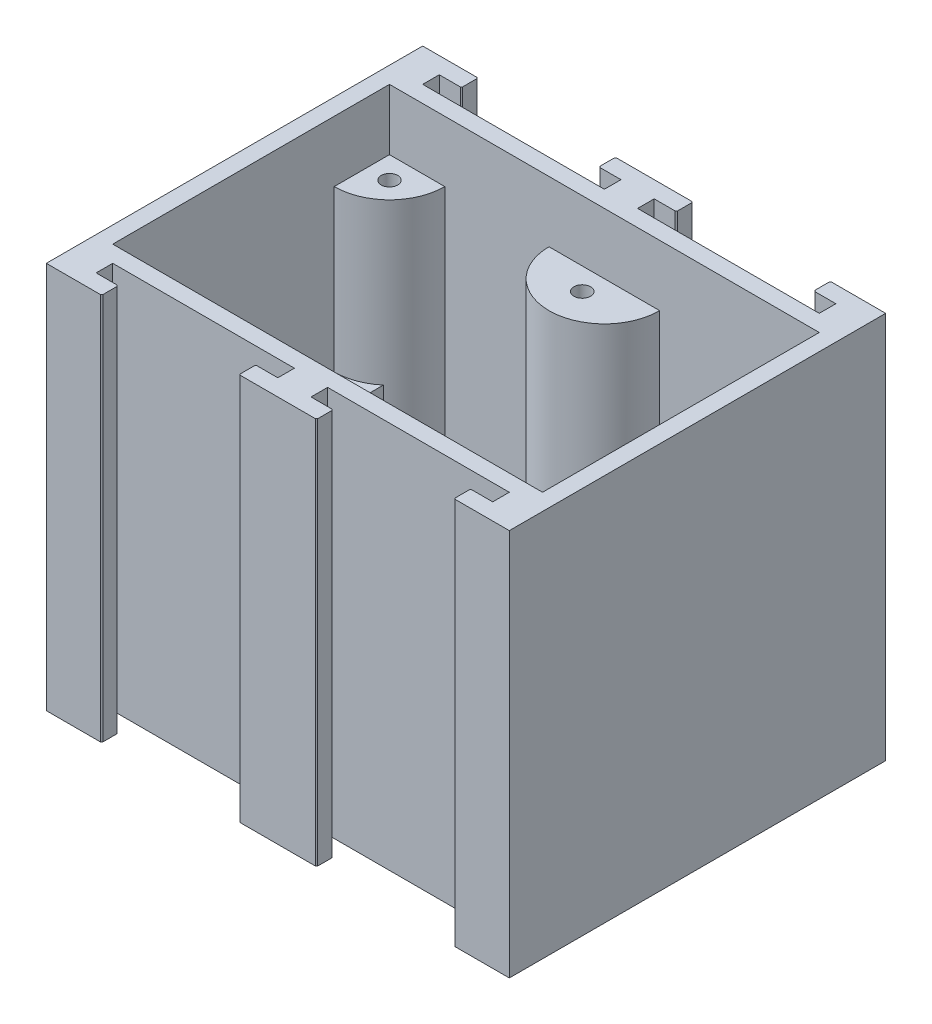
SolidWorks part; units mm, degrees
ref_plane "Front Plane" through (0, 0, 0) normal (0, 0, 1) x (1, 0, 0)
ref_plane "Top Plane" through (0, 0, 0) normal (0, 1, 0) x (1, 0, 0)
ref_plane "Right Plane" through (0, 0, 0) normal (1, 0, 0) x (0, 0, -1)
sketch "Sketch1" plane through (0, 0, 0) normal (0, 1, 0) x (1, 0, 0)
  line L0 (-38.825, 15) -> (-38.825, 25)
  line L1 (-38.825, -25) -> (-28.825, -25)
  line L2 (-38.825, -25) -> (-38.825, -15)
  line L3 (-38.825, 25) -> (-28.825, 25)
  line L4 (38.825, -25) -> (38.825, -15)
  line L5 (-38.825, -25) -> (38.825, 25) construction
  line L6 (-38.825, 25) -> (38.825, -25) construction
  line L7 (28.825, 25) -> (38.825, 25)
  line L8 (28.825, -25) -> (38.825, -25)
  line L9 (38.825, 15) -> (38.825, 25)
  line L10 (-38.825, -25) -> (-31.7539, -17.9289) construction
  line L11 (0, 0) -> (0, 50000) construction
  line L12 (0, 0) -> (-50000, 0) construction
  line L13 (10, -25) -> (-10, -25)
  line L14 (10, 25) -> (-10, 25)
  arc A0 (-28.825, -25) -> (-38.825, -15) centre (-38.825, -25) ccw
  arc A1 (-28.825, 25) -> (-38.825, 15) centre (-38.825, 25) cw
  arc A2 (38.825, -15) -> (28.825, -25) centre (38.825, -25) ccw
  arc A3 (38.825, 15) -> (28.825, 25) centre (38.825, 25) cw
  circle A4 centre (-34.825, -21) radius 1.5
  circle A5 centre (34.825, -21) radius 1.5
  circle A6 centre (34.825, 21) radius 1.5
  circle A7 centre (-34.825, 21) radius 1.5
  arc A8 (-10, -25) -> (10, -25) centre (0, -25) cw
  circle A9 centre (0, -21) radius 1.5
  circle A10 centre (0, 21) radius 1.5
  arc A11 (-10, 25) -> (10, 25) centre (0, 25) ccw
  point P0 (0, 0)
  dimension "D3" = 10
  dimension "D4" = 3
  dimension "D1" = 77.65
  dimension "D2" = 50
  dimension "D5" = 4
  dimension "D6" = 4
  dimension "D7" = 4
extrude "Boss-Extrude6" add sketch "Sketch1" along normal blind 59 contours L1 A0 L2 | A1 L3 L0 | A3 L9 L7 | L4 A2 L8 | A8 L13 A9 | L14 A11 A10 region at (-38.6836, 0, -20) region at (-38.6836, 0, 20) region at (33.825, 0, 24.8586) region at (33.825, 0, -24.8586) region at (0, 0, 24.7764) region at (0, 0, -15.2236)
sketch "Sketch2" plane through (0, 0, 0) normal (0, 1, 0) x (1, 0, 0)
  line L0 (-41.825, 28) -> (41.825, 28)
  line L1 (-38.825, -25) -> (38.825, -25)
  line L2 (-38.825, -25) -> (-38.825, 25)
  line L3 (-38.825, 25) -> (38.825, 25)
  line L4 (38.825, -25) -> (38.825, 25)
  line L5 (-38.825, -25) -> (38.825, 25) construction
  line L6 (-38.825, 25) -> (38.825, -25) construction
  line L7 (41.825, -28) -> (41.825, 28)
  line L8 (-41.825, -28) -> (41.825, -28)
  line L9 (-41.825, -28) -> (-41.825, 28)
  point P0 (0, 0)
  dimension "D2" = 83.65
  dimension "D3" = 56
  dimension "D1" = 3
extrude "Boss-Extrude7" add sketch "Sketch2" along normal blind 70
sketch "Sketch3" plane through (0, 0, 0) normal (0, 1, 0) x (1, 0, 0)
  line L0 (-38.825, 0) -> (-38.825, 19)
  line L1 (38.825, -25) -> (-38.825, -25) construction
  line L2 (38.825, -25) -> (38.825, 25) construction
  line L3 (38.825, 25) -> (-38.825, 25) construction
  line L4 (-38.825, -25) -> (-38.825, 25) construction
  line L5 (38.825, -25) -> (-38.825, 25) construction
  line L6 (38.825, 25) -> (-38.825, -25) construction
  line L7 (-38.825, 19) -> (-32.325, 19)
  line L8 (-38.825, 0) -> (-38.825, -19)
  line L9 (-38.825, -19) -> (-32.325, -19)
  line L10 (-32.325, -19) -> (-32.325, 19)
  line L11 (-11.513, 0) -> (-11.513, 50000) construction
  line L12 (-32.325, 0) -> (9.299, 0) construction
  line L13 (9.299, -25) -> (17.299, -25)
  line L14 (9.299, -25) -> (9.299, 25)
  line L15 (9.299, 25) -> (17.299, 25)
  line L16 (17.299, -25) -> (17.299, 25)
  line L17 (9.299, -25) -> (17.299, 25) construction
  line L18 (9.299, 25) -> (17.299, -25) construction
  circle A0 centre (-35.925, 4.8) radius 2.1
  circle A1 centre (-35.925, -4.8) radius 2.1
  circle A2 centre (12.899, -4.8) radius 2.1
  circle A3 centre (12.899, 4.8) radius 2.1
  point P0 (0, 0)
  point P18 (13.299, 0)
  point P25 (-11.513, 0)
  dimension "D5" = 4.2
  dimension "D1" = 6.5
  dimension "D2" = 38
  dimension "D4" = 2.9
  dimension "D6" = 9.299
  dimension "D7" = 8
extrude "Boss-Extrude8" add sketch "Sketch3" along normal blind 30
chamfer "Chamfer1" distance 3 angle 45 4 edges at (17.299, 15, 25) (13.6495, 30, 25) (17.299, 15, -25) (13.6495, 30, -25)
fillet "Fillet1" radius 3 2 edges at (9.299, 15, 21.3219) (9.299, 15, -21.3219)
sketch "Sketch4" plane through (0, 0, 0) normal (0, -1, 0) x (1, 0, 0)
  line L0 (-35.925, 4.8) -> (-35.925, -4.8) construction
  line L3 (-41.825, 28) -> (41.825, 28) construction
  line L4 (-28.825, 25) -> (-10, 25) construction
  line L5 (-35.925, 4.8) -> (12.899, 4.8) construction
  line L7 (-31.8835, 4.8) -> (-33.9043, 8.3)
  line L8 (-33.9043, 8.3) -> (-37.9457, 8.3)
  line L9 (-37.9457, 8.3) -> (-39.9665, 4.8)
  line L10 (-39.9665, 4.8) -> (-37.9457, 1.3)
  line L11 (-37.9457, 1.3) -> (-33.9043, 1.3)
  line L12 (-33.9043, 1.3) -> (-31.8835, 4.8)
  line L13 (-31.8835, -4.8) -> (-33.9043, -1.3)
  line L16 (-33.9043, -1.3) -> (-37.9457, -1.3)
  line L17 (-37.9457, -1.3) -> (-39.9665, -4.8)
  line L18 (-39.9665, -4.8) -> (-37.9457, -8.3)
  line L19 (-37.9457, -8.3) -> (-33.9043, -8.3)
  line L20 (-33.9043, -8.3) -> (-31.8835, -4.8)
  line L21 (-11.513, 4.8) -> (-11.513, 50004.8) construction
  line L22 (-37.9457, -8.3) -> (-39.9665, -4.8)
  line L23 (-31.8835, -4.8) -> (-33.9043, -8.3)
  line L24 (-33.9043, -1.3) -> (-31.8835, -4.8)
  line L25 (-39.9665, -4.8) -> (-37.9457, -1.3)
  line L26 (-37.9457, 1.3) -> (-39.9665, 4.8)
  line L27 (-31.8835, 4.8) -> (-33.9043, 1.3)
  line L28 (-33.9043, 8.3) -> (-31.8835, 4.8)
  line L29 (-39.9665, 4.8) -> (-37.9457, 8.3)
  line L30 (12.899, 4.8) -> (12.899, -4.8) construction
  line L31 (16.9405, 4.8) -> (14.9197, 8.3)
  line L32 (10.8783, 8.3) -> (8.8575, 4.8)
  line L33 (8.8575, 4.8) -> (10.8783, 1.3)
  line L34 (14.9197, 1.3) -> (16.9405, 4.8)
  line L35 (16.9405, -4.8) -> (14.9197, -1.3)
  line L36 (10.8783, -1.3) -> (8.8575, -4.8)
  line L37 (8.8575, -4.8) -> (10.8783, -8.3)
  line L38 (14.9197, -8.3) -> (16.9405, -4.8)
  line L39 (10.8783, -8.3) -> (8.8575, -4.8)
  line L40 (14.9197, -8.3) -> (10.8783, -8.3)
  line L41 (16.9405, -4.8) -> (14.9197, -8.3)
  line L42 (14.9197, -1.3) -> (16.9405, -4.8)
  line L43 (10.8783, -1.3) -> (14.9197, -1.3)
  line L44 (8.8575, -4.8) -> (10.8783, -1.3)
  line L45 (10.8783, 1.3) -> (8.8575, 4.8)
  line L46 (14.9197, 1.3) -> (10.8783, 1.3)
  line L47 (16.9405, 4.8) -> (14.9197, 1.3)
  line L48 (14.9197, 8.3) -> (16.9405, 4.8)
  line L49 (10.8783, 8.3) -> (14.9197, 8.3)
  line L50 (8.8575, 4.8) -> (10.8783, 8.3)
  circle A0 centre (-35.925, 4.8) radius 3.5 construction
  circle A1 centre (-35.925, -4.8) radius 3.5 construction
  circle A2 centre (12.899, -4.8) radius 3.5 construction
  circle A3 centre (12.899, 4.8) radius 3.5 construction
  point P24 (-11.513, 4.8)
  line M4 (9.299, 13.628) -> (9.299, -13.628)
  line M9 (-32.325, -17.4007) -> (-32.325, 17.4007)
  circle M20 centre (12.899, 4.8) radius 2.1
  circle M21 centre (12.899, -4.8) radius 2.1
  circle M22 centre (-35.925, -4.8) radius 2.1
  circle M23 centre (-35.925, 4.8) radius 2.1
  dimension "D1" = 3
  dimension "D2" = 7
  dimension "D3" = 7
extrude "Cut-Extrude2" cut sketch "Sketch4" against normal blind 16 contours L11 L12 L7 L8 L9 L10 M9 M23 | L19 L20 L13 L16 L17 L18 M9 M22 | L43 L36 L37 L40 L38 L35 M4 M21 | L49 L32 L33 L46 L34 L31 M4 M20 region at (-32.4286, 0, -4.8) region at (-32.4286, 0, 4.8) region at (15.8403, 0, 3.1018) region at (10.1784, 0, -2.7195)
fillet "Fillet2" radius 1.3 8 edges at (9.299, 8, -5.5646) (9.299, 8, 4.0354) (9.299, 8, -4.0354) (9.299, 8, 5.5646) (-32.325, 8, 5.5646) (-32.325, 8, -4.0354) (-32.325, 8, -5.5646) (-32.325, 8, 4.0354)
sketch "Sketch5" plane through (0, 0, 0) normal (0, -1, 0) x (1, 0, 0)
  line L0 (-35.925, 4.8) -> (-35.925, -4.8) construction
  line L1 (12.899, 4.8) -> (12.899, -4.8) construction
  line L2 (17.299, 22) -> (17.299, -22) construction
  line L3 (8.499, -6) -> (17.299, -6)
  line L4 (8.499, -6) -> (8.499, 6)
  line L5 (8.499, 6) -> (17.299, 6)
  line L6 (17.299, -6) -> (17.299, 6)
  line L7 (8.499, -6) -> (17.299, 6) construction
  line L8 (12.899, 0) -> (-35.925, 0) construction
  line L9 (-11.513, 0) -> (-11.513, 50000) construction
  line L10 (8.499, 6) -> (17.299, -6) construction
  line L11 (-31.525, 6) -> (-40.325, -6) construction
  line L12 (-31.525, -6) -> (-40.325, 6) construction
  line L13 (-35.925, 4.8) -> (-35.925, -4.8) construction
  line L14 (-40.325, -6) -> (-40.325, 6)
  line L15 (-31.525, 6) -> (-40.325, 6)
  line L16 (-31.525, -6) -> (-31.525, 6)
  line L17 (-31.525, -6) -> (-40.325, -6)
  point P4 (-35.925, 0)
  point P18 (-11.513, 0)
  dimension "D1" = 12
extrude "Cut-Extrude3" cut sketch "Sketch5" against normal blind 10
fillet "Fillet3" radius 0.6 8 edges at (-39.2736, 5, 6) (-40.325, 5, 6) (-39.2736, 5, -6) (-40.325, 5, -6) (16.2476, 5, -6) (17.299, 5, -6) (17.299, 5, 6) (16.2476, 5, 6)
sketch "Sketch6" plane through (0, 0, 0) normal (0, 1, 0) x (1, 0, 0)
  line L0 (0, 0) -> (0, 50000) construction
  line L1 (-41.825, -28) -> (41.825, -28) construction
  line L2 (-41.825, -28) -> (-41.825, 28) construction
  line L3 (-41.825, 28) -> (41.825, 28) construction
  line L4 (41.825, -28) -> (41.825, 28) construction
  line L5 (-41.825, -28) -> (41.825, 28) construction
  line L6 (-41.825, 28) -> (41.825, -28) construction
  line L7 (0, 0) -> (50000, 0) construction
  line L8 (38.825, 25) -> (-38.825, 25) construction
  line L9 (-3, 31) -> (3, 31)
  line L10 (-3, 31) -> (-3, 25)
  line L11 (-3, 25) -> (3, 25)
  line L12 (3, 31) -> (3, 25)
  line L13 (-3, 31) -> (3, 25) construction
  line L14 (-3, 25) -> (3, 31) construction
  line L15 (31.825, 31) -> (41.825, 34) construction
  line L16 (-7, 34) -> (7, 34)
  line L17 (-7, 34) -> (-7, 31)
  line L18 (-7, 31) -> (7, 31)
  line L19 (7, 34) -> (7, 31)
  line L20 (-7, 34) -> (7, 31) construction
  line L21 (-7, 31) -> (7, 34) construction
  line L22 (-35.825, 25) -> (-41.825, 25)
  line L23 (-35.825, 25) -> (-35.825, 31)
  line L24 (-35.825, 31) -> (-41.825, 31)
  line L25 (-41.825, 25) -> (-41.825, 31)
  line L26 (-35.825, 25) -> (-41.825, 31) construction
  line L27 (-35.825, 31) -> (-41.825, 25) construction
  line L28 (-31.825, 34) -> (-41.825, 34)
  line L29 (-31.825, 34) -> (-31.825, 31)
  line L30 (-31.825, 31) -> (-41.825, 31)
  line L31 (-41.825, 34) -> (-41.825, 31)
  line L32 (-31.825, 34) -> (-41.825, 31) construction
  line L33 (-31.825, 31) -> (-41.825, 34) construction
  line L34 (31.825, 34) -> (41.825, 31) construction
  line L35 (35.825, 31) -> (41.825, 25) construction
  line L36 (35.825, 25) -> (41.825, 31) construction
  line L37 (41.825, 34) -> (41.825, 31)
  line L38 (31.825, 31) -> (41.825, 31)
  line L39 (31.825, 34) -> (31.825, 31)
  line L40 (31.825, 34) -> (41.825, 34)
  line L41 (41.825, 25) -> (41.825, 31)
  line L42 (35.825, 31) -> (41.825, 31)
  line L43 (35.825, 25) -> (35.825, 31)
  line L44 (35.825, 25) -> (41.825, 25)
  line L45 (35.825, -25) -> (41.825, -31) construction
  line L46 (35.825, -31) -> (41.825, -25) construction
  line L47 (31.825, -34) -> (41.825, -31) construction
  line L48 (31.825, -31) -> (41.825, -34) construction
  line L49 (35.825, -25) -> (41.825, -25)
  line L50 (35.825, -25) -> (35.825, -31)
  line L51 (35.825, -31) -> (41.825, -31)
  line L52 (41.825, -25) -> (41.825, -31)
  line L53 (31.825, -34) -> (41.825, -34)
  line L54 (31.825, -34) -> (31.825, -31)
  line L55 (31.825, -31) -> (41.825, -31)
  line L56 (41.825, -34) -> (41.825, -31)
  line L57 (-31.825, -31) -> (-41.825, -34) construction
  line L58 (-31.825, -34) -> (-41.825, -31) construction
  line L59 (-35.825, -31) -> (-41.825, -25) construction
  line L60 (-35.825, -25) -> (-41.825, -31) construction
  line L61 (-41.825, -34) -> (-41.825, -31)
  line L62 (-31.825, -31) -> (-41.825, -31)
  line L63 (-31.825, -34) -> (-31.825, -31)
  line L64 (-31.825, -34) -> (-41.825, -34)
  line L65 (-41.825, -25) -> (-41.825, -31)
  line L66 (-35.825, -31) -> (-41.825, -31)
  line L67 (-35.825, -25) -> (-35.825, -31)
  line L68 (-35.825, -25) -> (-41.825, -25)
  line L69 (-7, -31) -> (7, -34) construction
  line L70 (-7, -34) -> (7, -31) construction
  line L71 (-3, -25) -> (3, -31) construction
  line L72 (-3, -31) -> (3, -25) construction
  line L73 (7, -34) -> (7, -31)
  line L74 (-7, -31) -> (7, -31)
  line L75 (-7, -34) -> (-7, -31)
  line L76 (-7, -34) -> (7, -34)
  line L77 (3, -31) -> (3, -25)
  line L78 (-3, -25) -> (3, -25)
  line L79 (-3, -31) -> (-3, -25)
  line L80 (-3, -31) -> (3, -31)
  point P0 (0, 0)
  point P11 (0, 28)
  point P18 (0, 32.5)
  point P24 (-38.825, 28)
  point P29 (-36.825, 32.5)
  point P40 (36.825, 32.5)
  point P41 (38.825, 28)
  point P49 (38.825, -28)
  point P50 (36.825, -32.5)
  point P58 (-36.825, -32.5)
  point P59 (-38.825, -28)
  point P68 (0, -32.5)
  point P69 (0, -28)
  dimension "D1" = 6
  dimension "D2" = 3
  dimension "D3" = 14
  dimension "D4" = 10
extrude "Boss-Extrude9" add sketch "Sketch6" along normal up to surface (70 mm away) contours L67 L68 L65 L62 | L64 L63 L62 L61 | L75 L76 L73 L74 | L53 L56 L51 L55 L54 | L43 L44 L41 L38 | L19 L16 L17 L18 L9 | L12 L9 L10 L11 | L25 L22 L23 L24 | L77 L78 L79 L80 | L52 L49 L50 L51 | L38 L39 L40 L37 | L30 L29 L28 L31 region at (0, 0, -32.5) region at (0, 0, -28) region at (-38.825, 0, -28) region at (38.825, 0, -28) region at (36.825, 0, 32.5) region at (-36.825, 0, 32.5) region at (-38.825, 0, 28) region at (0, 0, 32.5) up to face at (0, 70, 0)
chamfer "Chamfer3" distance 0.2 angle 45 16 edges at (-7, 35, 34) (-7, 35, 31) (-31.825, 35, 34) (-31.825, 35, 31) (7, 35, 34) (7, 35, 31) (31.825, 35, 34) (31.825, 35, 31) (31.825, 35, -31) (31.825, 35, -34) (7, 35, -31) (-7, 35, -31) (-7, 35, -34) (7, 35, -34) (-31.825, 35, -31) (-31.825, 35, -34)
